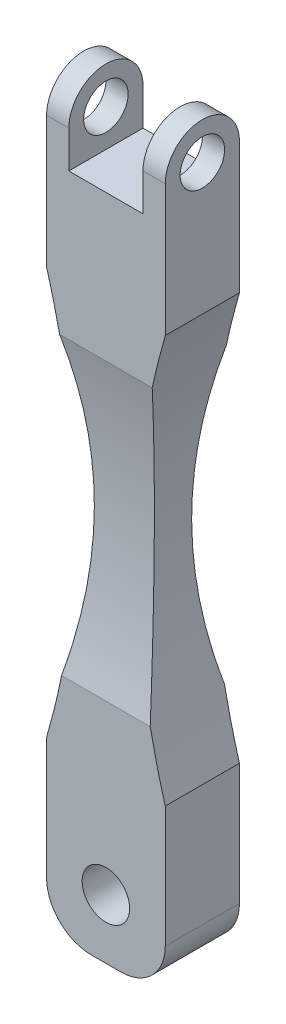
SolidWorks part; units mm, degrees
ref_plane "Front Plane" through (0, 0, 0) normal (0, 0, 1) x (1, 0, 0)
ref_plane "Top Plane" through (0, 0, 0) normal (0, 1, 0) x (1, 0, 0)
ref_plane "Right Plane" through (0, 0, 0) normal (1, 0, 0) x (0, 0, -1)
sketch "Sketch1" plane through (0, 0, 0) normal (0, 0, 1) x (1, 0, 0)
  line L1 (-1, -25) -> (1, -25)
  line L2 (-4, -22) -> (-4, 25)
  line L3 (-4, 25) -> (4, 25)
  line L4 (4, -22) -> (4, 25)
  line L5 (-4, -25) -> (4, 25) construction
  line L6 (-4, 25) -> (4, -25) construction
  arc A0 (1, -25) -> (4, -22) centre (1, -22) ccw
  arc A1 (-1, -25) -> (-4, -22) centre (-1, -22) cw
  circle A2 centre (0, -21) radius 1.6
  point P1 (0, 0)
  dimension "D3" = 3
  dimension "D4" = 3.2
  dimension "D1" = 50
  dimension "D2" = 8
  dimension "D5" = 4
  dimension "D6" = 4
extrude "Boss-Extrude1" add sketch "Sketch1" along normal blind 5
sketch "Sketch2" plane through (0, 0, 5) normal (0, 0, 1) x (1, 0, 0)
  line L0 (4, 25) -> (-4, 25) construction
  line L1 (-2.5, 25) -> (2.5, 25)
  line L2 (-2.5, 25) -> (-2.5, 20)
  line L3 (-2.5, 20) -> (2.5, 20)
  line L4 (2.5, 25) -> (2.5, 20)
  line L5 (-4, 25) -> (-4, -22) construction
  dimension "D1" = 5
  dimension "D2" = 5
  dimension "D3" = 1.5
extrude "Cut-Extrude1" cut sketch "Sketch2" against normal blind 11
fillet "Fillet4" 2 edges at (-3.25, 25, 5) (-3.25, 25, 0) type full round first side face at (0, 4.4757, 5) second side face at (0, 4.4757, 0) middle face at (-3.25, 25, 2.5)
fillet "Fillet5" 2 edges at (3.25, 25, 0) (3.25, 25, 5) type full round first side face at (0, 3.9757, 0) second side face at (0, 3.9757, 5) middle face at (3.25, 25, 2.5)
sketch "Sketch3" plane through (4, 0, 0) normal (1, 0, 0) x (0, 0, -1)
  circle A0 centre (-2.5, 22.5) radius 1.5
  dimension "D1" = 3
extrude "Cut-Extrude2" cut sketch "Sketch3" against normal blind 11
sketch "Sketch4" plane through (4, 0, 0) normal (1, 0, 0) x (0, 0, -1)
  line L0 (-2.5, 22.5) -> (-2.5, -29.669) construction
  line L1 (-5.9382, 13.3817) -> (-5.8544, -12.6614)
  line L2 (0.9382, 13.3817) -> (0.8544, -12.6614)
  spline S0 degree 2 poles (-5.9382, 13.3817) (-1.6247, 0.3547) (-5.8544, -12.6614) knots 0 0 0 1 1 1
  spline S1 degree 2 poles (0.9382, 13.3817) (-3.3753, 0.3547) (0.8544, -12.6614) knots 0 0 0 1 1 1
extrude "Cut-Extrude3" cut sketch "Sketch4" against normal blind 11
sketch "Sketch5" plane through (0, 0, 5) normal (0, 0, 1) x (1, 0, 0)
  line L0 (-5.2464, -17.6056) -> (-4.9437, 16.5967)
  line L1 (0, 7.012) -> (0, -2.6736) construction
  line L2 (5.2464, -17.6056) -> (4.9437, 16.5967)
  spline S0 degree 2 poles (-4.9437, 16.5967) (1.0558, -0.5256) (-5.2464, -17.6056) knots 0 0 0 1 1 1
  spline S1 degree 2 poles (4.9437, 16.5967) (-1.0558, -0.5256) (5.2464, -17.6056) knots 0 0 0 1 1 1
extrude "Cut-Extrude4" cut sketch "Sketch5" against normal blind 11
